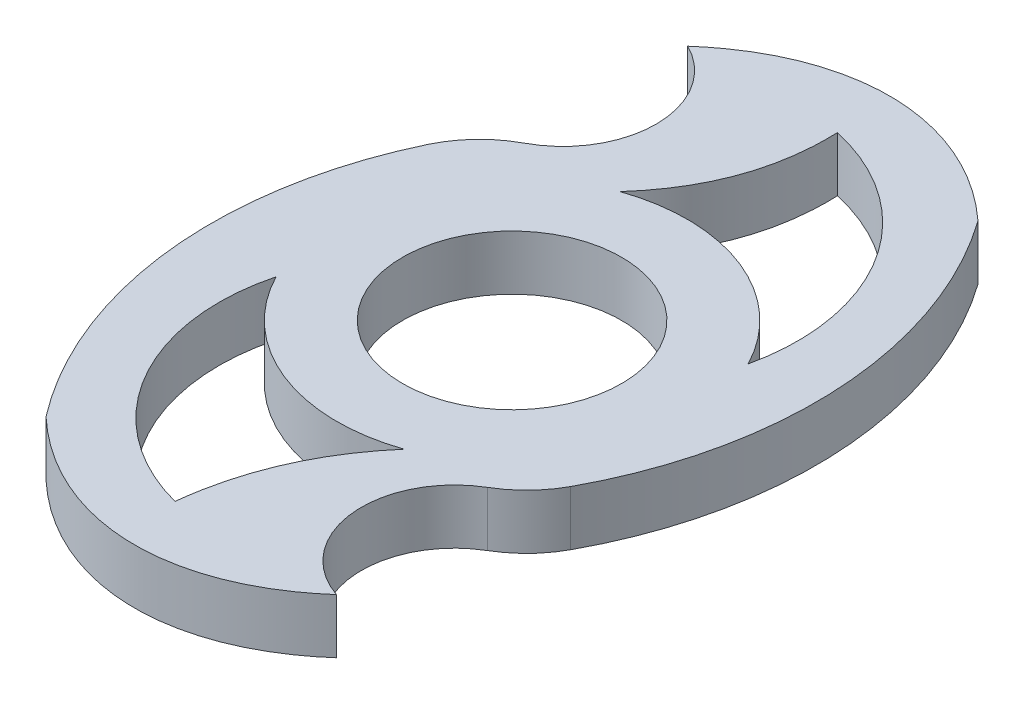
SolidWorks part; units mm, degrees
ref_plane "Front Plane" through (0, 0, 0) normal (0, 0, 1) x (1, 0, 0)
ref_plane "Top Plane" through (0, 0, 0) normal (0, 1, 0) x (1, 0, 0)
ref_plane "Right Plane" through (0, 0, 0) normal (1, 0, 0) x (0, 0, -1)
other "Center of Mass"
sketch "Sketch2" plane through (0, 0, 0) normal (0, 1, 0) x (1, 0, 0)
  line L0 (45.3395, 28.2226) -> (45.4294, 28.2226)
  line L1 (25.5392, 59.4089) -> (27.329, 59.4089)
  line L3 (-27.329, -59.4089) -> (-25.5392, -59.4089)
  line L4 (27.329, 59.4089) -> (27.329, 57.7974)
  line L5 (26.8098, 58.2801) -> (27.329, 59.4089) construction
  line L6 (-27.329, -59.4089) -> (-26.8098, -58.2801) construction
  line L8 (-45.4294, -27.9485) -> (-45.4294, -27.7518)
  line L9 (-45.4294, -27.7518) -> (-45.4933, -27.7518)
  line L10 (45.4294, 28.2226) -> (45.4294, 27.9485)
  line L12 (-45.4294, -27.7518) -> (-45.4827, -27.7847) construction
  line L14 (-27.329, -57.7974) -> (-27.329, -59.4089)
  line L16 (45.3546, 28.1765) -> (45.4294, 28.2226) construction
  line L20 (-10.5211, 30.2209) -> (10.5211, -30.2209) construction
  line L21 (-10.5211, -30.2209) -> (10.5211, 30.2209) construction
  line L26 (-28.4473, 14.6545) -> (28.4473, -14.6545) construction
  line L27 (-28.4473, -14.6545) -> (28.4473, 14.6545) construction
  arc A0 (-26.8874, 29.1742) -> (-27.329, 59.4089) centre (-34.8801, 44.178) ccw
  arc A1 (24.1727, -28.6501) -> (27.329, -59.4089) centre (32.7838, -43.3078) ccw
  arc A2 (-35.5394, 20.1252) -> (-27.329, -57.7974) centre (32.1681, -12.1346) ccw
  arc A3 (26.8098, 58.2801) -> (31.6238, -20.9389) centre (-34.308, 14.8103) cw
  arc A4 (-35.5394, 20.1252) -> (-26.8874, 29.1742) centre (-17.4841, 11.5226) cw
  arc A5 (24.1727, -28.6501) -> (31.6238, -20.9389) centre (14.042, -11.4057) ccw
  circle A6 centre (0, 0) radius 20
  arc A7 (-28.4473, -14.6545) -> (10.5211, -30.2209) centre (0, 0) ccw
  arc A8 (-2.1528, -59.4089) -> (-28.4473, -14.6545) centre (7.0772, -23.8845) cw
  arc A9 (0, 59.4089) -> (28.4473, 14.6545) centre (-8.1536, 22.8081) cw
  arc A10 (28.4473, 14.6545) -> (-10.5211, 30.2209) centre (0, 0) ccw
  ellipse E0 centre (0, 0) end of major axis (2.1528, -69.9669) minor radius 50 (-45.4933, -27.7518) -> (-45.4294, -27.9485) ccw
  ellipse E1 centre (0, 0) end of major axis (2.1528, -69.9669) minor radius 50 (45.4294, 27.9485) -> (45.3395, 28.2226) ccw
  ellipse E2 centre (0, 0) end of major axis (2.1528, -69.9669) minor radius 50 (27.329, 57.7974) -> (-27.329, 59.4089) ccw
  ellipse E3 centre (0, 0) end of major axis (2.1528, -69.9669) minor radius 50 (-27.329, -57.7974) -> (27.329, -59.4089) ccw
  spline S0 degree 2 poles (-10.5211, 30.2209) (0.6634, 42.7177) (0, 59.4089) knots 0 0 0 1 1 1
  spline S1 degree 2 poles (10.5211, -30.2209) (-0.3301, -42.8254) (-2.1528, -59.4089) knots 0 0 0 1 1 1
  dimension "D1" = 20
  dimension "D2" = 20
extrude "Boss-Extrude1" add sketch "Sketch2" along normal blind 10 contours A2 E3 A1 A5 A3 E2 A0 A4 A6 region at (25.0964, 0, -57.6312)
